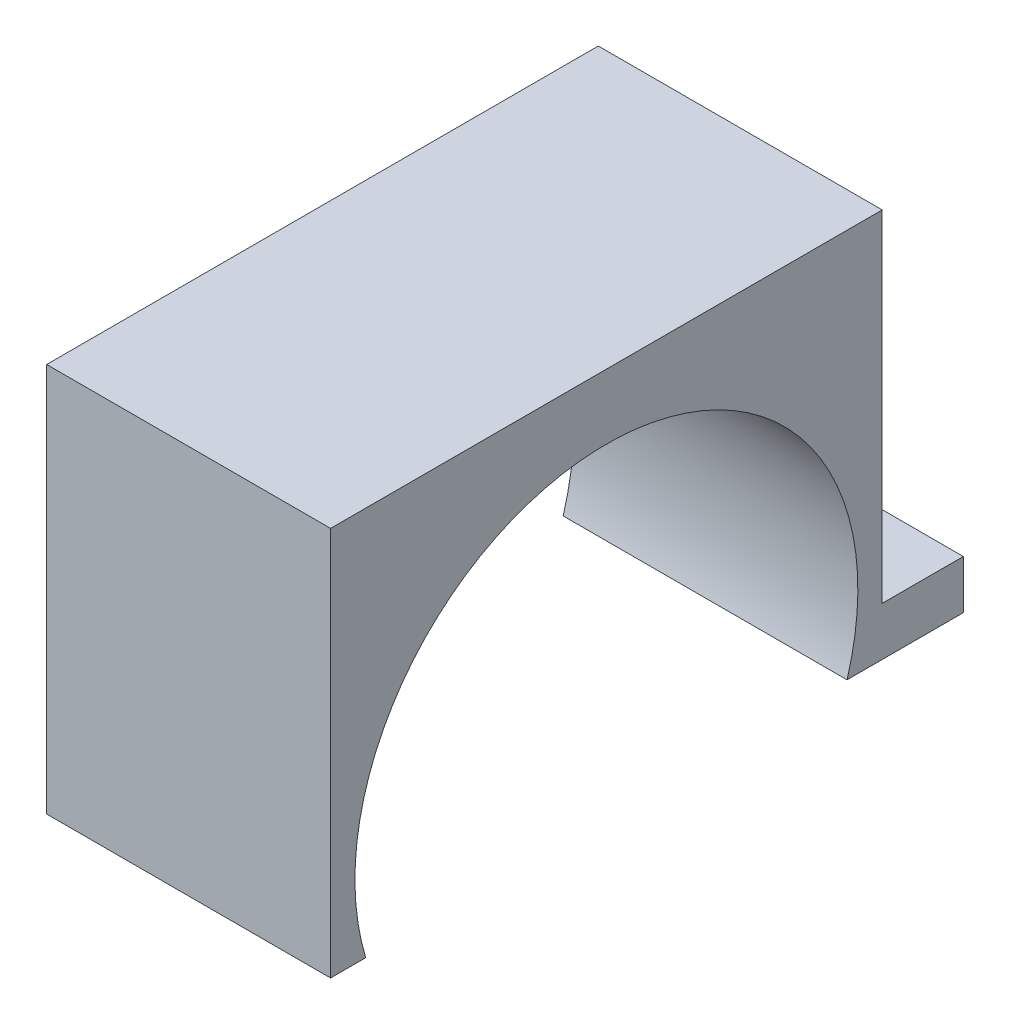
SolidWorks part; units mm, degrees
ref_plane "前视基准面" through (0, 0, 0) normal (0, 0, 1) x (1, 0, 0)
ref_plane "上视基准面" through (0, 0, 0) normal (0, 1, 0) x (1, 0, 0)
ref_plane "右视基准面" through (0, 0, 0) normal (1, 0, 0) x (0, 0, -1)
sketch "草图1" plane through (0, 0, 0) normal (0, 1, 0) x (1, 0, 0)
  line L1 (0, 0) -> (17, 0)
  line L2 (0, 0) -> (0, -40)
  line L3 (0, -40) -> (17, -40)
  line L4 (17, 0) -> (17, -40)
  dimension "D1" = 17
  dimension "D2" = 40
extrude "凸台-拉伸1" add sketch "草图1" along normal blind 50
sketch "草图2" plane through (0, 0, 0) normal (0, -1, 0) x (1, 0, 0)
  line L0 (0, 39) -> (0, 40)
  line L1 (-0.5, 39) -> (17, 39) construction
  line L2 (0, 0) -> (0, 40) construction
  line L3 (0, 40) -> (17, 40)
  line L4 (17, 40) -> (17, 39)
  line L5 (17, 40) -> (17, 0) construction
  line L6 (17, 39) -> (0, 39)
extrude "切除-拉伸1" cut sketch "草图2" against normal through all
sketch "草图4" plane through (0, 0, 0) normal (0, -1, 0) x (1, 0, 0)
  line L0 (0, 39) -> (-0.5, 39)
  line L1 (-0.5, 39) -> (-0.5, 0)
  line L2 (-0.5, 0) -> (0, 0)
  line L3 (0, 0) -> (0, 39)
extrude "凸台-拉伸2" add sketch "草图4" against normal up to vertex (50 mm away) up to point (0, 50, 39)
sketch "草图5" plane through (17, 0, 0) normal (1, 0, 0) x (0, 0, -1)
  circle A0 centre (-22, 4.5) radius 15.5
extrude "切除-拉伸2" cut sketch "草图5" against normal up to vertex (17.5 mm away) up to point (-0.5, 0, 39)
sketch "草图6" plane through (17, 0, 0) normal (1, 0, 0) x (0, 0, -1)
  line L0 (0, 24) -> (0, 3)
  line L2 (-22, 24) -> (-5, 24)
  line L3 (0, 50) -> (0, 0) construction
  line L4 (0, 24) -> (0, 50)
  line L5 (0, 50) -> (-39, 50)
  line L6 (-39, 50) -> (-39, 24)
  line L7 (-39, 50) -> (-39, 0) construction
  line L8 (-39, 24) -> (-22, 24)
  line L9 (0, 0) -> (0, 3)
  line L10 (0, 3) -> (-5, 3)
  line L11 (-5, 3) -> (-5, 24)
  line L12 (0, 24) -> (0, 3)
  line M11 (0, 0) -> (0, 50)
  line M12 (0, 50) -> (-39, 50)
  line M13 (-39, 50) -> (-39, 0)
extrude "切除-拉伸3" cut sketch "草图6" against normal up to vertex (17.5 mm away) contours L11 L10 L8 L2 M11 M12 M13 region at (17, 34.7949, 17.9048) up to point (-0.5, 50, 0)
sketch "草图7" plane through (0, 3, 0) normal (0, 1, 0) x (1, 0, 0)
  line L0 (8.25, -5) -> (8.25, 0)
  line L1 (-0.5, -5) -> (17, -5) construction
  line L2 (-0.5, 0) -> (17, 0) construction
  circle A0 centre (8.25, -2.5) radius 1.6
extrude "切除-拉伸4" cut sketch "草图7" against normal up to vertex (3 mm away) contours L0 A0 | L0 A0 region at (7.5709, 3, 2.5) region at (8.9291, 3, 2.5) up to point (17, 0, 0)
